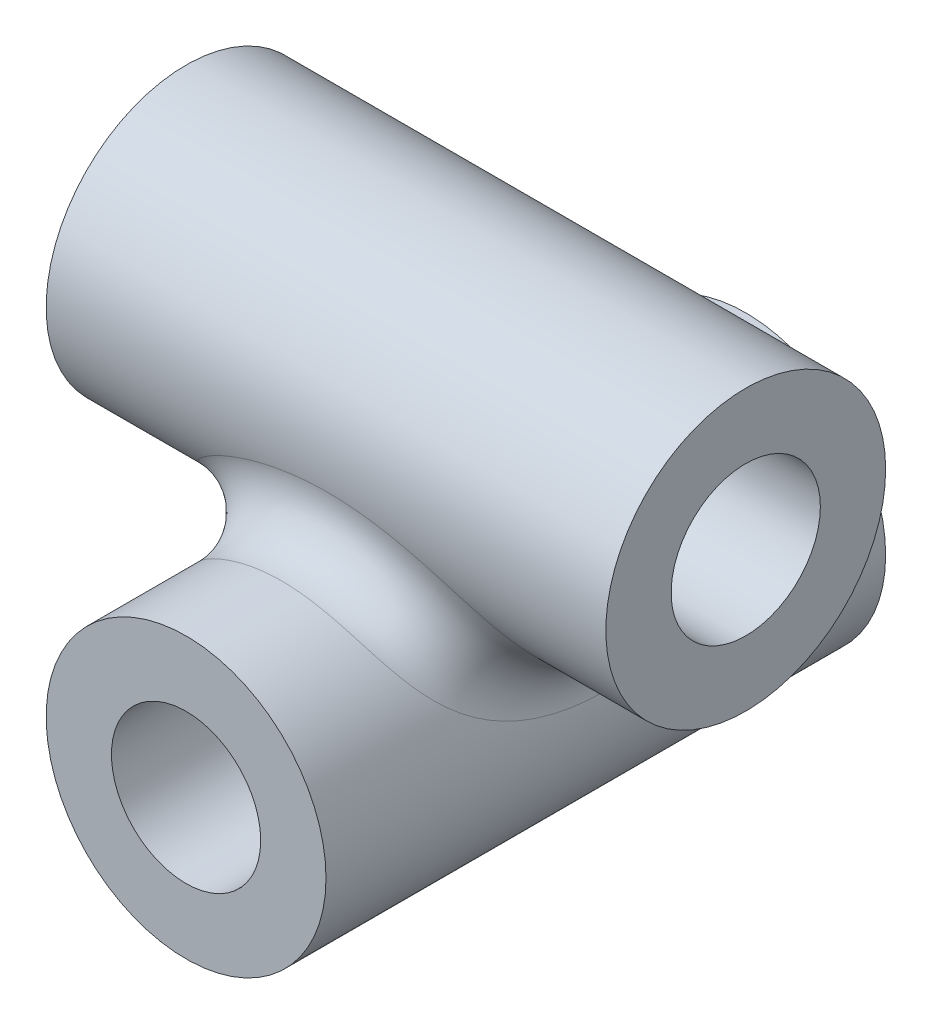
SolidWorks part; units mm, degrees
ref_plane "Front Plane" through (0, 0, 0) normal (0, 0, 1) x (1, 0, 0)
ref_plane "Top Plane" through (0, 0, 0) normal (0, 1, 0) x (1, 0, 0)
ref_plane "Right Plane" through (0, 0, 0) normal (1, 0, 0) x (0, 0, -1)
sketch "Sketch1" plane through (0, 0, 0) normal (0, 0, 1) x (1, 0, 0)
  circle A0 centre (0, 0) radius 8
  circle A1 centre (0, 0) radius 15
  dimension "D1" = 16
  dimension "D2" = 30
extrude "Boss-Extrude1" add sketch "Sketch1" along normal blind 60
sketch "Sketch2" plane through (0, 0, 0) normal (1, 0, 0) x (0, 0, -1)
  line L0 (-30, -15) -> (-30, 49985) construction
  line L1 (-60, -15) -> (0, -15) construction
  line L2 (-30, 23) -> (-50030, 23) construction
  line L3 (0, 0) -> (-50000, 0) construction
  circle A0 centre (-30, 23) radius 8
  circle A1 centre (-30, 23) radius 15
  point P4 (-30, -15)
  dimension "D2" = 30
  dimension "D3" = 16
  dimension "D1" = 23
extrude "Boss-Extrude2" add sketch "Sketch2" along normal mid plane 60
fillet "Fillet1" radius 5 1 edges at (-3.3823, 14.6137, 17.5634)
